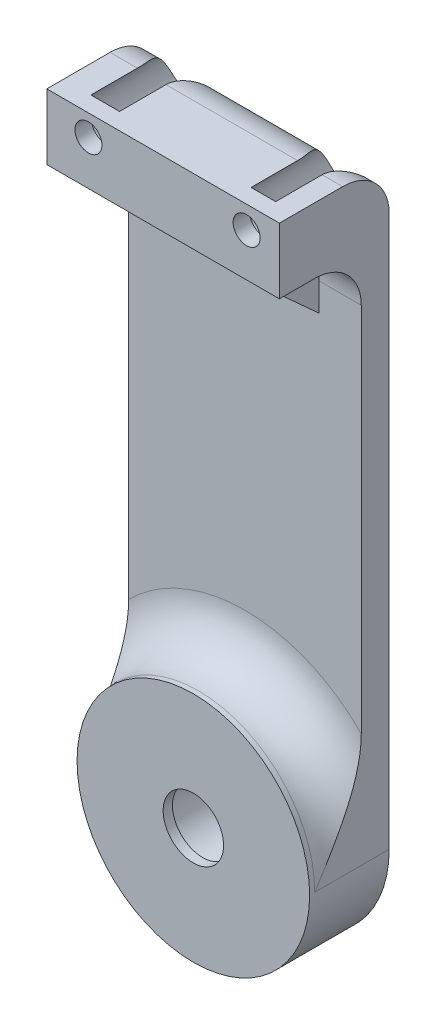
SolidWorks part; units mm, degrees
ref_plane "Plano frontal" through (0, 0, 0) normal (0, 0, 1) x (1, 0, 0)
ref_plane "Plano superior" through (0, 0, 0) normal (0, 1, 0) x (1, 0, 0)
ref_plane "Plano direito" through (0, 0, 0) normal (1, 0, 0) x (0, 0, -1)
sketch "Esboço2" plane through (0, 0, 0) normal (0, 0, 1) x (1, 0, 0)
  circle A0 centre (-0.4749, -0.0634) radius 12.5
extrude "Ressalto-extrusão1" add sketch "Esboço2" against normal offset from surface (5.55 mm away) 2 offset beyond the face yes
sketch "Esboço4" plane through (0, 0, -5.55) normal (0, 0, -1) x (-1, 0, 0)
  line L0 (-12.0251, -0.0634) -> (-12.0251, 64.1202)
  line L1 (12.9749, -0.0634) -> (12.9749, 64.1202)
  line L2 (12.9749, 64.1202) -> (-12.0251, 64.1202)
  arc A0 (-12.0251, -0.0634) -> (12.9749, -0.0634) centre (0.4749, -0.0634) ccw
  circle A4 centre (0.4749, -0.0634) radius 12.5 construction
  dimension "D1" = 0.5
extrude "Ressalto-extrusão3" add sketch "Esboço4" along normal blind 3
sketch "Esboço5" plane through (0, 0, -8.55) normal (0, 0, -1) x (-1, 0, 0)
  line L0 (12.9749, -0.0634) -> (12.9749, 64.1202) construction
  line L1 (-12.0251, 64.1202) -> (12.9749, 64.1202)
  line L2 (-12.0251, 64.1202) -> (-12.0251, 57.0691)
  line L3 (-12.0251, 57.0691) -> (12.9749, 57.0691)
  line L5 (12.9749, 57.0691) -> (12.9749, 64.1202)
extrude "Ressalto-extrusão4" add sketch "Esboço5" against normal up to surface (11.8 mm away)
hole_wizard "Rebaixo para SHCS M2.51" positions "Esboço6" profile "Esboço7" counterbore size "M2.5" standard "Ansi Metric" end condition up to next
sketch "Esboço6" plane through (0, 0, -8.55) normal (0, 0, -1) x (-1, 0, 0)
  circle A0 centre (-8.4995, 61.7078) radius 1.35 construction
  circle A1 centre (8.5, 61.8383) radius 1.35 construction
  point P0 (-8.4995, 61.7078)
  point P2 (8.5, 61.8383)
sketch "Esboço7" plane through (8.4995, 61.7078, -8.55) normal (1, 0, 0) x (0, 1, 0)
  line L0 (0, 0) -> (0, 11.8)
  line L1 (0, 11.8) -> (1.45, 11.8)
  line L3 (1.45, 11.8) -> (1.45, 10)
  line L4 (1.45, 10) -> (2.75, 10)
  line L5 (2.75, 10) -> (2.75, 0)
  line L7 (2.75, 0) -> (0, 0)
  line L11 (0, -6.35) -> (0, 107.95) construction
  dimension "Thru Hole Dia." = 2.9
  dimension "Thru Hole Depth" = 11.8
  dimension "C'Bore Dia." = 5.5
  dimension "C'Bore Depth" = 10
sketch "Esboço10" plane through (0, 0, 0) normal (1, 0, 0) x (0, 0, -1)
  line L0 (-3.25, 57.0691) -> (5.55, 49.0691)
  line L1 (5.55, -0.0634) -> (5.55, 57.0691) construction
  line L2 (-3.25, 57.0691) -> (5.55, 57.0691) construction
  dimension "D1" = 8
rib "Nervura1" sketch "Esboço10" sketch "Esboço10" thickness 15 extrusion direction parallel to sketch draft on no parameters "D1"=15
sketch "Esboço11" plane through (0, 0, -5.55) normal (0, 0, 1) x (1, 0, 0)
  line L0 (7.5, 49.0691) -> (-7.5, 49.0691) construction
  line L1 (4.5, 49.0691) -> (-4.5, 49.0691)
  line L2 (4.5, 49.0691) -> (4.5, 57.0691)
  line L3 (4.5, 57.0691) -> (-4.5, 57.0691)
  line L4 (-4.5, 49.0691) -> (-4.5, 57.0691)
  line L5 (7.5, 57.0691) -> (-7.5, 57.0691) construction
  line L6 (7.5, 57.0691) -> (7.5, 49.0691) construction
  point P8 (0, 57.0691)
  point P9 (0, 57.0691)
  dimension "D1" = 3
extrude "Corte-extrusão1" cut sketch "Esboço11" along normal up to next
sketch "Esboço12" plane through (0, 0, -8.55) normal (0, 0, -1) x (-1, 0, 0)
  circle A0 centre (0.4749, -0.0634) radius 3.25 construction
  circle A1 centre (0.4749, -0.0634) radius 3.25
extrude "Corte-extrusão2" cut sketch "Esboço12" against normal through all
sketch "Esboço13" plane through (0, 0, -8.55) normal (0, 0, -1) x (-1, 0, 0)
  circle A0 centre (0.4749, -0.0634) radius 4 construction
  circle A1 centre (0.4749, -0.0634) radius 4
extrude "Corte-extrusão3" cut sketch "Esboço13" against normal offset from surface (7.55 mm away) 1 up to face at (2.7751, -0.0634, 0)
fillet "Filete1" radius 5 5 edges at (-0.4749, 12.4366, -5.55) (10.9224, 64.1202, -8.55) (-11.5048, 64.1202, -8.55) (0.107, 64.1202, -8.55) (-10.2375, 57.0691, -5.55)
fillet "Filete3" radius 5 2 edges at (9.7625, 57.0691, -5.55) (0, 57.0691, -5.55)
